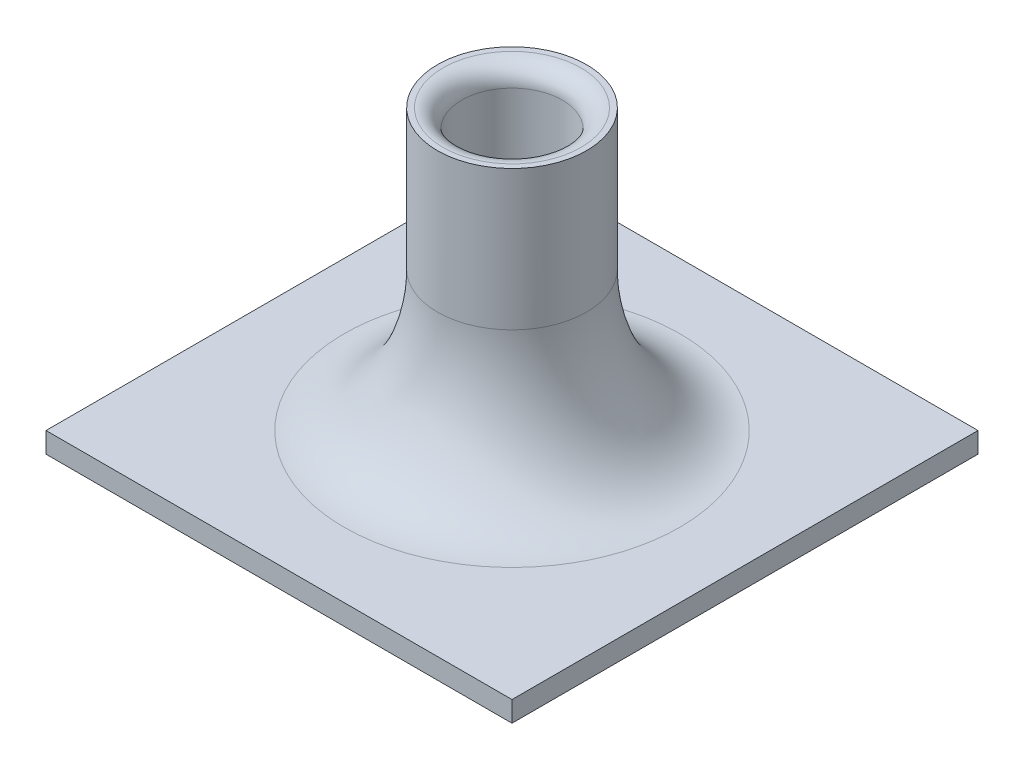
SolidWorks part; units mm, degrees
ref_plane "Спереди" through (0, 0, 0) normal (0, 0, 1) x (1, 0, 0)
ref_plane "Сверху" through (0, 0, 0) normal (0, 1, 0) x (1, 0, 0)
ref_plane "Справа" through (0, 0, 0) normal (1, 0, 0) x (0, 0, -1)
sketch "Эскиз1" plane through (0, 0, 0) normal (0, 1, 0) x (1, 0, 0)
  line L1 (-25, -25) -> (25, -25)
  line L2 (-25, -25) -> (-25, 25)
  line L3 (-25, 25) -> (25, 25)
  line L4 (25, -25) -> (25, 25)
  line L5 (0, 25) -> (0, -25) construction
  line L6 (-25, 0) -> (25, 0) construction
  point P0 (0, 0)
  dimension "D1" = 50
  dimension "D2" = 50
extrude "Бобышка-Вытянуть1" add sketch "Эскиз1" along normal blind 5
sketch "Эскиз5" plane through (0, 5, 0) normal (0, 1, 0) x (1, 0, 0)
  line L0 (0, 45.2463) -> (0, -39.6744) construction
  line L2 (-25, -25) -> (25, -25) construction
  circle A0 centre (0, 0) radius 8
  dimension "D1" = 25
  dimension "D2" = 16
extrude "Бобышка-Вытянуть3" add sketch "Эскиз5" along normal blind 30
sketch "Эскиз6" plane through (0, 35, 0) normal (0, 1, 0) x (1, 0, 0)
  circle A0 centre (0, 0) radius 5.4
  dimension "D1" = 10.8
extrude "Вырез-Вытянуть2" cut sketch "Эскиз6" against normal through all
fillet "Скругление3" radius 2 1 edges at (0, 35, 5.4)
fillet "Скругление2" radius 10 1 edges at (0, 5, 8) second distance 15 first distance on face at (0, 5, 8)
chamfer "Фаска1" distance 6 angle 25 5 edges at (0, 0, -25) (-25, 0, 0) (0, 0, 25) (25, 0, 0) (0, 0, 5.4) first distance on face at (0, 0, 5.4) first distance on face at (0, 33, 5.4)
